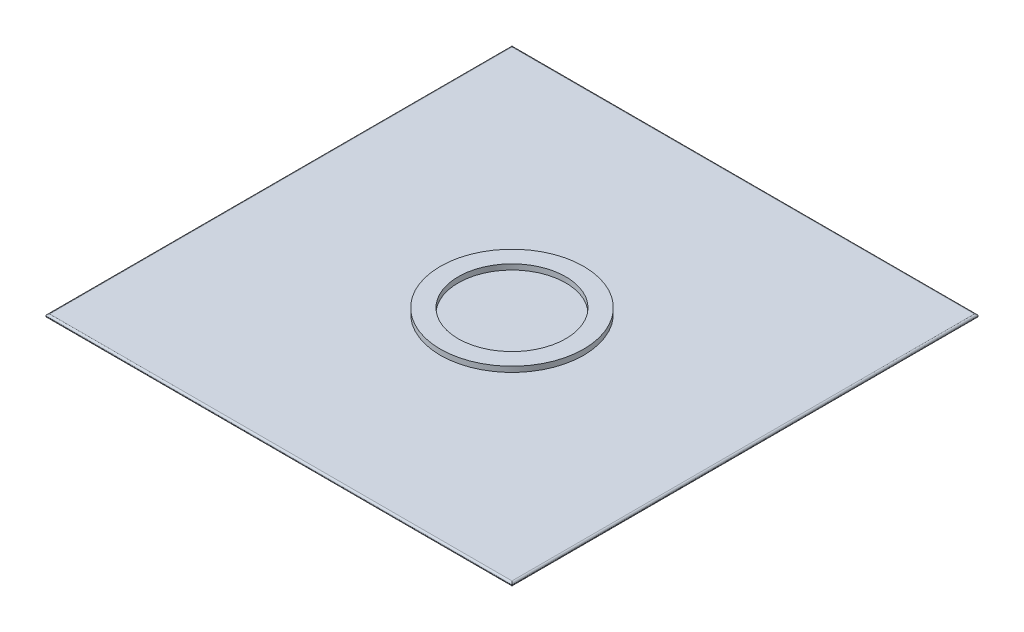
SolidWorks part; units mm, degrees
ref_plane "Front Plane" through (0, 0, 0) normal (0, 0, 1) x (1, 0, 0)
ref_plane "Top Plane" through (0, 0, 0) normal (0, 1, 0) x (1, 0, 0)
ref_plane "Right Plane" through (0, 0, 0) normal (1, 0, 0) x (0, 0, -1)
other "Configuration Table"
sketch "Sketch1" plane through (0, 0, 0) normal (0, 1, 0) x (1, 0, 0)
  line L0 (2574.005, 1300) -> (0, 1300) construction
  line L1 (0, 0) -> (2600, 0)
  line L2 (0, 0) -> (0, 2600)
  line L3 (0, 2600) -> (2600, 2600)
  line L4 (2600, 0) -> (2600, 2600)
  line L5 (1300, 2600) -> (1300, 0) construction
  point P8 (1300, 1300)
  dimension "D1" = 1300
extrude "Boss-Extrude1" add sketch "Sketch1" along normal blind 20
fillet "Fillet1" radius 10 4 edges at (1300, 20, -2600) (2600, 20, -1300) (1300, 20, 0) (0, 20, -1300)
fillet "Fillet2" radius 10 4 edges at (1300, 0, 0) (2600, 0, -1300) (1300, 0, -2600) (0, 0, -1300)
ref_plane "Plane1" through (0, 0, -1300) normal (0, 0, -1) x (-1, 0, 0)
ref_plane "Plane2" through (1300, 0, 0) normal (-1, 0, 0) x (0, 0, 1)
sketch "Sketch6" plane through (0, 0, -1300) normal (0, 0, -1) x (-1, 0, 0)
  line L0 (-1000, 20) -> (-900, 20)
  line L1 (-2590, 20) -> (-10, 20) construction
  line L2 (-1300, -1089) -> (-1300, 1089) construction
  line L3 (-1300, 325.5555) -> (-1300, -51.2691) construction
  line L4 (-900, 20) -> (-900, 50)
  line L5 (-900, 50) -> (-1000, 50)
  line L6 (-1000, 50) -> (-1000, 20)
  dimension "D2" = 300
  dimension "D3" = 900
  dimension "D4" = 30
  dimension "D5" = 100
revolve "Revolve1" add sketch "Sketch6" angle 360 about L3
